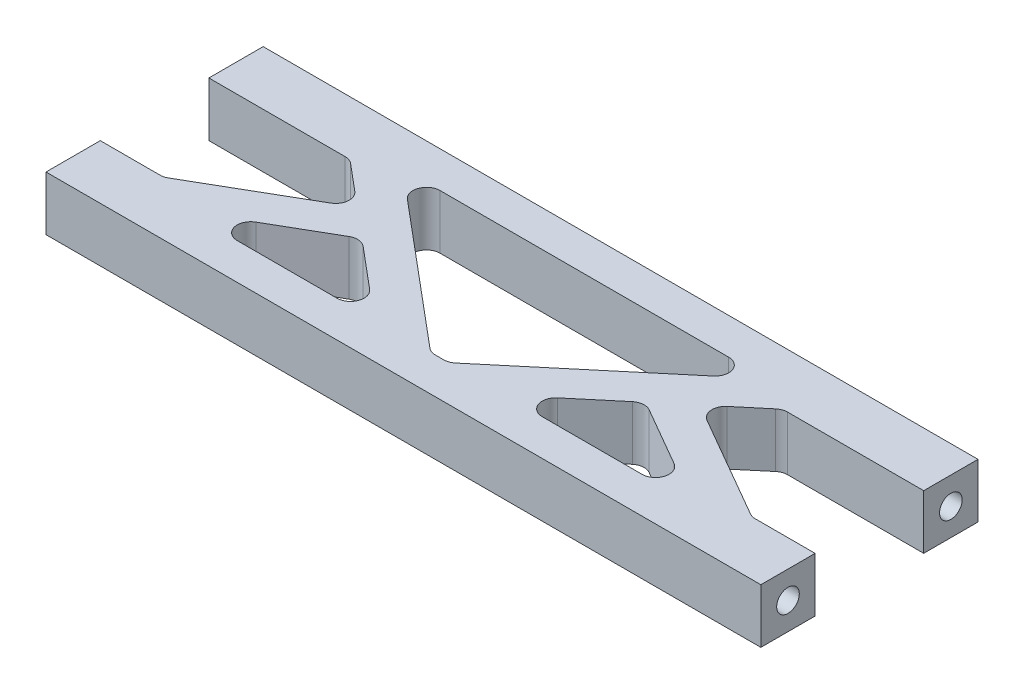
SolidWorks part; units mm, degrees
material "1060 Alloy"
ref_plane "Front Plane" through (0, 0, 0) normal (0, 0, 1) x (1, 0, 0)
ref_plane "Top Plane" through (0, 0, 0) normal (0, 1, 0) x (1, 0, 0)
ref_plane "Right Plane" through (0, 0, 0) normal (1, 0, 0) x (0, 0, -1)
sketch "Sketch1" plane through (0, 0, 0) normal (0, 1, 0) x (1, 0, 0)
  line L1 (0, 0) -> (79, 0)
  line L2 (0, 0) -> (0, 24)
  line L3 (0, 24) -> (79, 24)
  line L4 (79, 0) -> (79, 24)
  dimension "D1" = 24
  dimension "D2" = 79
extrude "Boss-Extrude1" add sketch "Sketch1" along normal blind 6
sketch "Sketch2" plane through (0, 6, 0) normal (0, 1, 0) x (1, 0, 0)
  line L0 (0, 18) -> (15.5926, 18)
  line L2 (0, 24) -> (0, 0) construction
  line L3 (19.4319, 20) -> (59.5681, 20)
  line L4 (7, 6) -> (0, 6)
  line L6 (0, 6) -> (0, 18)
  line L7 (79, 18) -> (63.4074, 18)
  line L8 (79, 0) -> (79, 24) construction
  line L9 (59.5681, 20) -> (40.5, 4)
  line L10 (72, 6) -> (79, 6)
  line L11 (79, 6) -> (79, 18)
  line L12 (40.5, 4) -> (38.5, 4)
  line L13 (38.5, 4) -> (19.4319, 20)
  line L14 (15.5926, 18) -> (20.5621, 13.8301)
  line L15 (20.5621, 13.8301) -> (7, 6)
  line L16 (79, 24) -> (0, 24) construction
  line L17 (0, 0) -> (79, 0) construction
  line L18 (23.8229, 11.0939) -> (11.5359, 4)
  line L19 (11.5359, 4) -> (32.2771, 4)
  line L20 (32.2771, 4) -> (23.8229, 11.0939)
  line L21 (46.7229, 4) -> (55.1771, 11.0939)
  line L22 (55.1771, 11.0939) -> (67.4641, 4)
  line L23 (67.4641, 4) -> (46.7229, 4)
  line L24 (72, 6) -> (58.4379, 13.8301)
  line L25 (58.4379, 13.8301) -> (63.4074, 18)
  dimension "D4" = 4
  dimension "D5" = 4
  dimension "D1" = 6
  dimension "D2" = 6
  dimension "D3" = 4
  dimension "D6" = 4
  dimension "D7" = 4
  dimension "D8" = 4
  dimension "D9" = 2
  dimension "D10" = 30
  dimension "D11" = 7
  dimension "D12" = 40
extrude "Cut-Extrude1" cut sketch "Sketch2" against normal up to next
hole_wizard "Tap Drill for M3 Tap1" positions "Sketch4" profile "Sketch3" hole size "M3" standard "ISO"
sketch "Sketch4" plane through (0, 0, 0) normal (-1, 0, 0) x (0, 0, 1)
  line L0 (-24, 0) -> (-18, 0) construction
  line L1 (-24, 6) -> (-24, 0) construction
  line L2 (0, 6) -> (0, 0) construction
  point P0 (-21, 3)
  point P2 (-3, 3)
  dimension "D1" = 3
  dimension "D2" = 3
  dimension "D3" = 3
sketch "Sketch3" plane through (0, 3, -21) normal (0, 1, 0) x (0, 0, 1)
  line L0 (0, 0) -> (0, 10.7511)
  line L1 (0, 10.7511) -> (1.25, 10)
  line L2 (1.25, 10) -> (1.25, 0)
  line L5 (1.25, 0) -> (0, 0)
  line L10 (0, 10.7511) -> (-1.25, 10) construction
  line L11 (0, -6.35) -> (0, 107.95) construction
  dimension "Hole Dia." = 2.5
  dimension "Hole Depth" = 10
  dimension "Drill Angle" = 118
hole_wizard "Tap Drill for M3 Tap2" positions "Sketch6" profile "Sketch5" hole size "M3" standard "ISO"
sketch "Sketch6" plane through (79, 0, 0) normal (1, 0, 0) x (0, 0, -1)
  line L0 (0, 0) -> (6, 0) construction
  line L1 (0, 6) -> (0, 0) construction
  line L2 (24, 6) -> (24, 0) construction
  point P0 (3, 3)
  point P2 (21, 3)
  dimension "D1" = 3
  dimension "D2" = 3
  dimension "D3" = 3
sketch "Sketch5" plane through (79, 3, -3) normal (0, 1, 0) x (0, 0, -1)
  line L0 (0, 0) -> (0, 10.7511)
  line L1 (0, 10.7511) -> (1.25, 10)
  line L2 (1.25, 10) -> (1.25, 0)
  line L5 (1.25, 0) -> (0, 0)
  line L10 (0, 10.7511) -> (-1.25, 10) construction
  line L11 (0, -6.35) -> (0, 107.95) construction
  dimension "Hole Dia." = 2.5
  dimension "Hole Depth" = 10
  dimension "Drill Angle" = 118
fillet "Fillet1" radius 1.5 16 edges at (46.7229, 3, -4) (55.1771, 3, -11.0939) (72, 3, -6) (58.4379, 3, -13.8301) (63.4074, 3, -18) (59.5681, 3, -20) (40.5, 3, -4) (38.5, 3, -4) (19.4319, 3, -20) (32.2771, 3, -4) (23.8229, 3, -11.0939) (7, 3, -6) (20.5621, 3, -13.8301) (15.5926, 3, -18) (67.4641, 3, -4) (11.5359, 3, -4)
